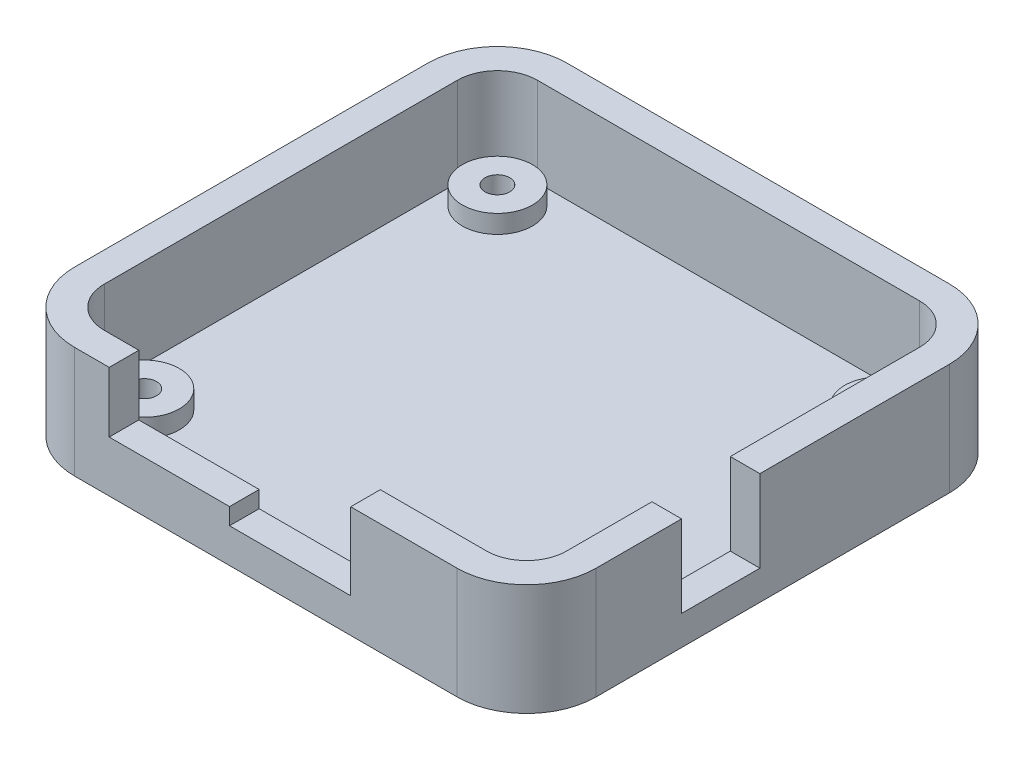
SolidWorks part; units mm, degrees
ref_plane "Front Plane" through (0, 0, 0) normal (0, 0, 1) x (1, 0, 0)
ref_plane "Top Plane" through (0, 0, 0) normal (0, 1, 0) x (1, 0, 0)
ref_plane "Right Plane" through (0, 0, 0) normal (1, 0, 0) x (0, 0, -1)
sketch "Sketch1" plane through (0, 0, 0) normal (0, 1, 0) x (1, 0, 0)
  line L0 (3.556, 0.5) -> (42.304, 0.5)
  line L1 (3.556, 0) -> (42.304, 0)
  line L2 (0, -3.556) -> (0, -39.344)
  line L3 (3.556, -42.9) -> (42.304, -42.9)
  line L4 (45.86, -3.556) -> (45.86, -39.344)
  line L5 (46.36, -3.556) -> (46.36, -39.344)
  line L6 (3.556, -43.4) -> (42.304, -43.4)
  line L7 (-0.5, -3.556) -> (-0.5, -39.344)
  line L8 (3.556, 3.5) -> (42.304, 3.5)
  line L9 (49.36, -3.556) -> (49.36, -39.344)
  line L10 (3.556, -46.4) -> (42.304, -46.4)
  line L11 (-3.5, -3.556) -> (-3.5, -39.344)
  arc A0 (42.304, 0) -> (45.86, -3.556) centre (42.304, -3.556) cw
  arc A1 (45.86, -39.344) -> (42.304, -42.9) centre (42.304, -39.344) cw
  arc A2 (3.556, -42.9) -> (0, -39.344) centre (3.556, -39.344) cw
  arc A3 (0, -3.556) -> (3.556, 0) centre (3.556, -3.556) cw
  circle A4 centre (3.556, -3.556) radius 1.25
  circle A5 centre (42.304, -3.556) radius 1.25
  circle A6 centre (42.304, -39.344) radius 1.25
  circle A7 centre (3.556, -39.344) radius 1.25
  arc A8 (42.304, 0.5) -> (46.36, -3.556) centre (42.304, -3.556) cw
  arc A9 (46.36, -39.344) -> (42.304, -43.4) centre (42.304, -39.344) cw
  arc A10 (3.556, -43.4) -> (-0.5, -39.344) centre (3.556, -39.344) cw
  arc A11 (-0.5, -3.556) -> (3.556, 0.5) centre (3.556, -3.556) cw
  arc A12 (42.304, 3.5) -> (49.36, -3.556) centre (42.304, -3.556) cw
  arc A13 (49.36, -39.344) -> (42.304, -46.4) centre (42.304, -39.344) cw
  arc A14 (3.556, -46.4) -> (-3.5, -39.344) centre (3.556, -39.344) cw
  arc A15 (-3.5, -3.556) -> (3.556, 3.5) centre (3.556, -3.556) cw
  circle A16 centre (3.556, -3.556) radius 3.55
  circle A17 centre (42.304, -3.556) radius 3.55
  circle A18 centre (42.304, -39.344) radius 3.55
  circle A19 centre (3.556, -39.344) radius 3.55
  point P8 (45.86, 0)
  point P13 (0, -42.9)
  point P16 (0, 0)
  dimension "D3" = 3.556
  dimension "D4" = 2.5
  dimension "D5" = 2.5
  dimension "D6" = 2.5
  dimension "D7" = 2.5
  dimension "D1" = 42.9
  dimension "D2" = 45.86
  dimension "D8" = 0.5
  dimension "D9" = 3
  dimension "D10" = 2.3
extrude "Boss-Extrude1" add sketch "Sketch1" along normal blind 2.3 contours A15 L11 A14 L10 A13 L9 A12 L8 L7 A11 L0 A8 L5 A9 L6 A10 | A11 L7 A10 L6 A9 L5 A8 L0 L2 A3 L1 A0 L4 A1 L3 A2 | A3 L2 A2 L3 A1 L4 A0 L1 A19 A18 A17 A16 | A18 A6 | A19 A7 | A16 A4 | A17 A5 region at (22.93, 0, -0.4358) region at (22.93, 0, 21.45) region at (22.93, 0, -2.7731) region at (0.1064, 0, 3.556) region at (38.8544, 0, 3.556) region at (38.8544, 0, 39.344) region at (0.1064, 0, 39.344)
extrude "Boss-Extrude2" add sketch "Sketch1<3>" along normal blind 1.85 from surface contours A16 A4 | A17 A5 | A18 A6 | A19 A7 region at (0.1064, 0, 3.556) region at (38.8544, 0, 3.556) region at (38.8544, 0, 39.344) region at (0.1064, 0, 39.344) starting at face at (22.93, 2.3, 21.45)
sketch "Sketch1<3>" plane through (0, 0, 0) normal (0, 1, 0) x (1, 0, 0) same geometry as "Sketch1"
extrude "Boss-Extrude3" add sketch "Sketch1<4>" along normal blind 9 from surface contours A15 L11 A14 L10 A13 L9 A12 L8 L7 A11 L0 A8 L5 A9 L6 A10 region at (22.93, 0, -2.7731) starting at face at (42.304, 2.3, 42.894)
sketch "Sketch1<4>" plane through (0, 0, 0) normal (0, 1, 0) x (1, 0, 0) same geometry as "Sketch1"
sketch "Sketch2" plane through (49.36, 0, 0) normal (1, 0, 0) x (0, 0, -1)
  line L0 (-3.556, 0) -> (-39.344, 0) construction
  line L1 (-30.694, 11.3) -> (-22.756, 11.3)
  line L2 (-30.694, 11.3) -> (-30.694, 3)
  line L3 (-30.694, 3) -> (-22.756, 3)
  line L4 (-22.756, 11.3) -> (-22.756, 3)
  line L5 (-39.344, 11.3) -> (-3.556, 11.3) construction
  line L6 (-39.344, 11.3) -> (-39.344, 0) construction
  line L7 (-3.556, 11.3) -> (-3.556, 0) construction
  dimension "D1" = 3
  dimension "D2" = 0
  dimension "D3" = 8.65
  dimension "D4" = 19.2
extrude "Cut-Extrude3" cut sketch "Sketch2" against normal up to next
sketch "Sketch3" plane through (0, 0, 46.4) normal (0, 0, 1) x (1, 0, 0)
  line L0 (3.556, 11.3) -> (3.556, 0) construction
  line L1 (7.056, 11.3) -> (20.104, 11.3)
  line L2 (7.056, 11.3) -> (7.056, 5.18)
  line L3 (7.056, 5.18) -> (20.104, 5.18)
  line L4 (20.104, 11.3) -> (20.104, 5.18)
  line L5 (42.304, 11.3) -> (42.304, 0) construction
  line L6 (42.304, 11.3) -> (3.556, 11.3) construction
  line L8 (3.556, 0) -> (42.304, 0) construction
  dimension "D1" = 3.5
  dimension "D2" = 22.2
  dimension "D3" = 0
  dimension "D4" = 5.18
extrude "Cut-Extrude4" cut sketch "Sketch3" against normal up to next
sketch "Sketch4" plane through (0, 0, 46.4) normal (0, 0, 1) x (1, 0, 0)
  line L0 (3.556, 0) -> (42.304, 0) construction
  line L1 (31.534, 11.3) -> (19.254, 11.3)
  line L2 (31.534, 11.3) -> (31.534, 3.49)
  line L3 (31.534, 3.49) -> (19.254, 3.49)
  line L4 (19.254, 11.3) -> (19.254, 3.49)
  line L5 (42.304, 11.3) -> (20.104, 11.3) construction
  line L6 (42.304, 11.3) -> (42.304, 0) construction
  dimension "D1" = 3.49
  dimension "D2" = 0
  dimension "D3" = 10.77
  dimension "D4" = 12.28
extrude "Cut-Extrude5" cut sketch "Sketch4" against normal up to next
